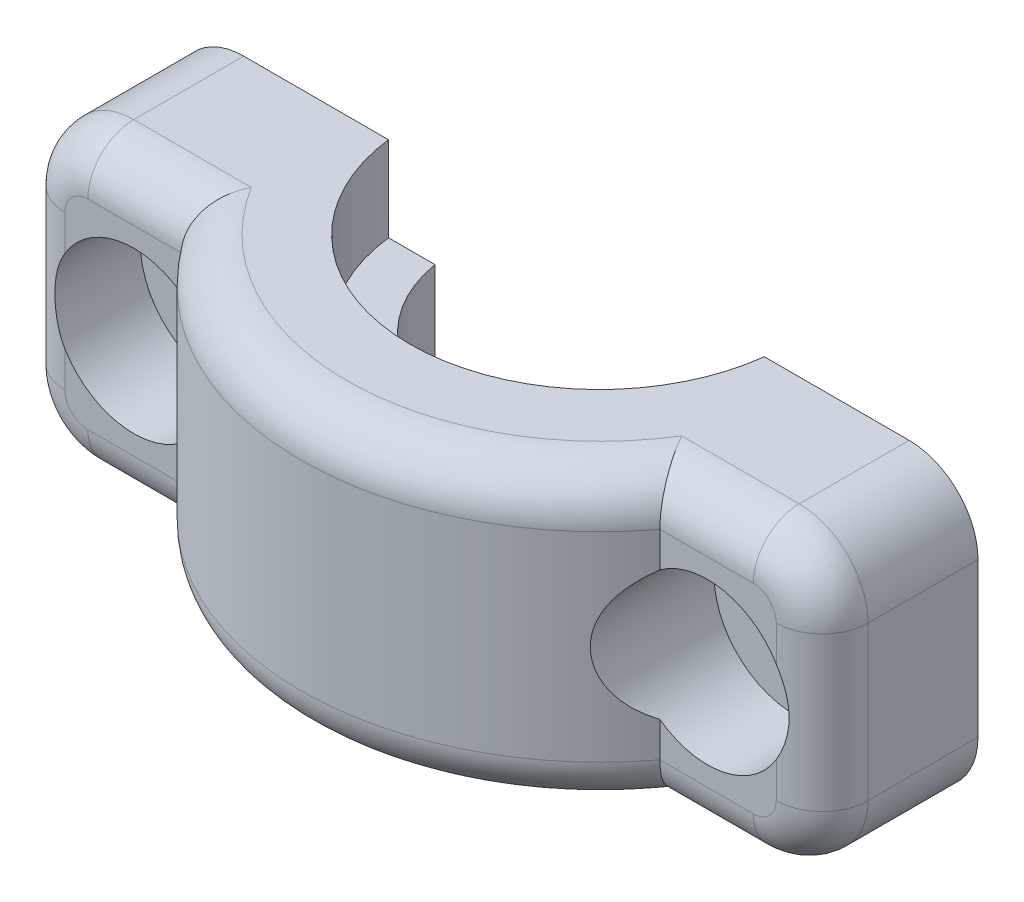
SolidWorks part; units mm, degrees
material "ABS"
ref_plane "Front Plane" through (0, 0, 0) normal (0, 0, 1) x (1, 0, 0)
ref_plane "Top Plane" through (0, 0, 0) normal (0, 1, 0) x (1, 0, 0)
ref_plane "Right Plane" through (0, 0, 0) normal (1, 0, 0) x (0, 0, -1)
sketch "Sketch1" plane through (0, 0, 0) normal (0, 0, 1) x (1, 0, 0)
  line L1 (-17.5, -6.35) -> (17.5, -6.35)
  line L2 (-17.5, -6.35) -> (-17.5, 6.35)
  line L3 (-17.5, 6.35) -> (17.5, 6.35)
  line L4 (17.5, -6.35) -> (17.5, 6.35)
  line L5 (-17.5, -6.35) -> (17.5, 6.35) construction
  line L6 (-17.5, 6.35) -> (17.5, -6.35) construction
  circle A0 centre (12.5, 0) radius 1.75
  circle A1 centre (-12.5, 0) radius 1.75
  point P0 (0, 0)
  dimension "D1" = 12.5
  dimension "D2" = 25
  dimension "D5" = 3.5
  dimension "D3" = 35
  dimension "D4" = 12.7
extrude "Boss-Extrude1" add sketch "Sketch1" along normal blind 12
sketch "Sketch2" plane through (0, 6.35, 0) normal (0, 1, 0) x (1, 0, 0)
  line L0 (17.5, 0) -> (-17.5, 0) construction
  circle A0 centre (0, 1) radius 8.25
  dimension "D2" = 16.5
  dimension "D1" = 1
extrude "Cut-Extrude1" cut sketch "Sketch2" against normal blind 3.7
sketch "Sketch3" plane through (0, 2.65, 0) normal (0, 1, 0) x (1, 0, 0)
  circle A0 centre (0, 1.0412) radius 6.25
  dimension "D1" = 12.5
extrude "Cut-Extrude2" cut sketch "Sketch3" against normal blind 5.7
sketch "Sketch4" plane through (0, -3.05, 0) normal (0, 1, 0) x (1, 0, 0)
  circle A0 centre (0, 1.0412) radius 8.25
  dimension "D1" = 16.5
extrude "Cut-Extrude3" cut sketch "Sketch4" against normal blind 6
sketch "Sketch5" plane through (0, 0, 12) normal (0, 0, 1) x (1, 0, 0)
  circle A0 centre (-12.5, 0) radius 3.5
  circle A1 centre (12.5, 0) radius 3.5
  dimension "D1" = 7
  dimension "D2" = 7
extrude "Cut-Extrude4" cut sketch "Sketch5" against normal offset from surface (9 mm away) 3 up to face at (10.009, -0.1, 0)
sketch "Sketch6" plane through (0, -6.35, 0) normal (0, -1, 0) x (1, 0, 0)
  line L0 (17.5, 0) -> (0, 0)
  line L1 (17.5, 0) -> (17.5, 6.7912)
  line L2 (17.5, 12) -> (17.5, 0) construction
  line L3 (17.5, 6.7912) -> (10.4272, 6.7912)
  line L4 (-17.5, 12) -> (-17.5, 0) construction
  line L5 (-17.5, 6.7912) -> (-17.5, 0)
  line L6 (-17.5, 0) -> (0, 0)
  line L7 (-10.4272, 6.7912) -> (-17.5, 6.7912)
  line L8 (-17.5, 12) -> (17.5, 12) construction
  line L9 (17.5, 6.7912) -> (17.5, 12)
  line L10 (17.5, 12) -> (-17.5, 12)
  line L11 (-17.5, 12) -> (-17.5, 6.7912)
  arc A0 (10.4272, 6.7912) -> (-10.4272, 6.7912) centre (0, -1.0412) ccw
  arc A3 (6.1627, 0) -> (-6.1627, 0) centre (0, -1.0412) ccw construction
  line M8 (17.5, 0) -> (17.5, 12)
  line M9 (17.5, 12) -> (-17.5, 12)
  line M10 (-17.5, 12) -> (-17.5, 0)
  dimension "D1" = 6.7912
  dimension "D2" = 6.7912
extrude "Cut-Extrude5" cut sketch "Sketch6" against normal blind 20 contours A0 L3 M8 M9 | A0 L10 L7 M10 region at (12.1102, -6.35, 9.7384) region at (-12.1102, -6.35, 9.7384)
fillet "Fillet1" radius 3 4 edges at (17.5, 6.35, 3.3956) (17.5, -6.35, 3.3956) (-17.5, -6.35, 3.3956) (-17.5, 6.35, 3.3956)
fillet "Fillet2" radius 2 12 edges at (-12.4636, 6.35, 6.7912) (-16.6213, 5.4713, 6.7912) (-17.5, 0, 6.7912) (-16.6213, -5.4713, 6.7912) (12.4636, 6.35, 6.7912) (16.6213, 5.4713, 6.7912) (17.5, 0, 6.7912) (16.6213, -5.4713, 6.7912) (0, 6.35, 12) (0, -6.35, 12) (-12.4636, -6.35, 6.7912) (12.4636, -6.35, 6.7912)
equation "\"D1@Sketch6\"=\"D2@Sketch6\""
